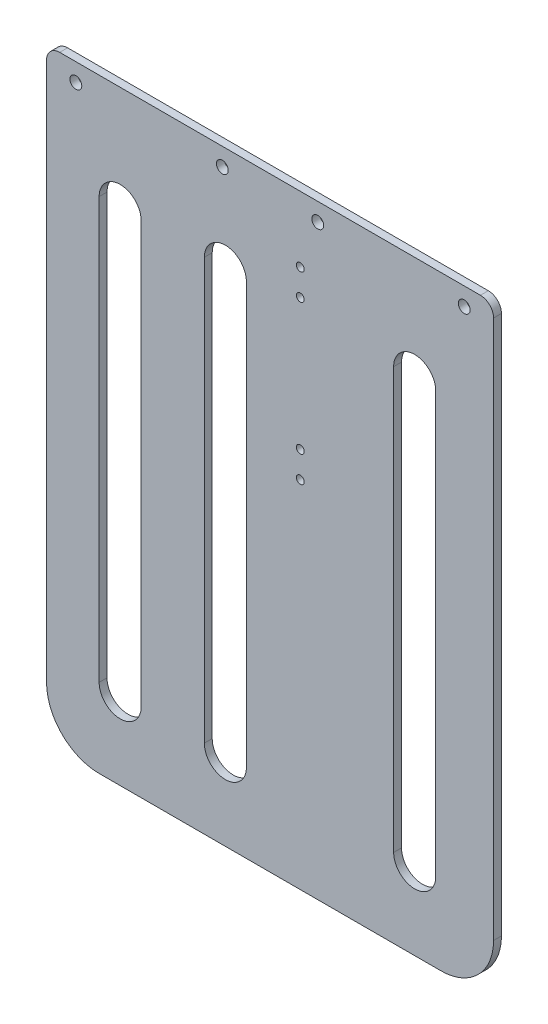
SolidWorks part; units mm, degrees
ref_plane "前视基准面" through (0, 0, 0) normal (0, 0, 1) x (1, 0, 0)
ref_plane "上视基准面" through (0, 0, 0) normal (0, 1, 0) x (1, 0, 0)
ref_plane "右视基准面" through (0, 0, 0) normal (1, 0, 0) x (0, 0, -1)
sketch "草图1" plane through (0, 0, 0) normal (0, 0, 1) x (1, 0, 0)
  line L1 (-85, 100) -> (85, 100)
  line L2 (-85, 100) -> (-85, -100)
  line L3 (-85, -100) -> (85, -100)
  line L4 (85, 100) -> (85, -100)
  line L5 (-85, 100) -> (85, -100) construction
  line L6 (-85, -100) -> (85, 100) construction
  point P0 (0, 0)
  dimension "D1" = 170
  dimension "D2" = 200
extrude "凸台-拉伸1" add sketch "草图1" along normal blind 3
sketch "草图2" plane through (0, 0, 0) normal (0, 0, -1) x (-1, 0, 0)
  circle A0 centre (-18.15, 93.15) radius 2.25 construction
  circle A1 centre (-73.85, 93.15) radius 2.25 construction
  circle A2 centre (18.15, 93.15) radius 2.25 construction
  circle A3 centre (73.85, 93.15) radius 2.25 construction
  circle A8 centre (-18.15, 93.15) radius 2.25
  circle A9 centre (-73.85, 93.15) radius 2.25
  circle A10 centre (18.15, 93.15) radius 2.25
  circle A11 centre (73.85, 93.15) radius 2.25
extrude "切除-拉伸1" cut sketch "草图2" against normal blind 10
sketch "草图4" plane through (0, 0, 0) normal (0, 0, -1) x (-1, 0, 0)
  line L1 (-85, -100) -> (85, -100)
  line L2 (-85, -100) -> (-85, -130)
  line L3 (-85, -130) -> (85, -130)
  line L4 (85, -100) -> (85, -130)
  dimension "D1" = 30
  dimension "D2" = 170
extrude "凸台-拉伸2" add sketch "草图4" against normal up to surface (3 mm away) up to face at (76.1, 93.15, 3)
sketch "草图5" plane through (0, 0, 3) normal (0, 0, 1) x (1, 0, 0)
  line L0 (55, -100) -> (55, 60) construction
  line L1 (47, -100) -> (47, 60)
  line L2 (63, -100) -> (63, 60)
  line L3 (85, -130) -> (85, 100) construction
  line L4 (85, -130) -> (-85, -130) construction
  line L5 (-17, -100) -> (-17, 60) construction
  line L6 (-25, -100) -> (-25, 60)
  line L7 (-9, -100) -> (-9, 60)
  line L8 (55, -100) -> (-17, -100) construction
  line L9 (-57, -100) -> (-57, 60) construction
  line L10 (-65, -100) -> (-65, 60)
  line L11 (-49, -100) -> (-49, 60)
  line L12 (-17, -100) -> (-57, -100) construction
  arc A0 (47, -100) -> (63, -100) centre (55, -100) ccw
  arc A1 (63, 60) -> (47, 60) centre (55, 60) ccw
  arc A2 (-25, -100) -> (-9, -100) centre (-17, -100) ccw
  arc A3 (-9, 60) -> (-25, 60) centre (-17, 60) ccw
  arc A4 (-65, -100) -> (-49, -100) centre (-57, -100) ccw
  arc A5 (-49, 60) -> (-65, 60) centre (-57, 60) ccw
  point P2 (55, -20)
  point P15 (-17, -20)
  point P23 (-57, -20)
  dimension "D1" = 16
  dimension "D2" = 30
  dimension "D3" = 30
  dimension "D4" = 160
  dimension "D6" = 72
  dimension "D8" = 40
  dimension "D5" = 2
  dimension "D7" = 2
extrude "切除-拉伸2" cut sketch "草图5" against normal through all
fillet "圆角1" radius 20 2 edges at (85, -130, 1.5) (-85, -130, 1.5)
fillet "圆角2" radius 5 2 edges at (85, 100, 1.5) (-85, 100, 1.5)
sketch "草图6" plane through (0, 0, 3) normal (0, 0, 1) x (1, 0, 0)
  circle A0 centre (11.5, 5) radius 1.5
  circle A1 centre (11.5, 15) radius 1.5
  circle A2 centre (11.5, 65) radius 1.5
  circle A3 centre (11.5, 75) radius 1.5
  dimension "D1" = 3
  dimension "D2" = 3
  dimension "D3" = 3
  dimension "D4" = 3
extrude "切除-拉伸3" cut sketch "草图6" against normal through all
